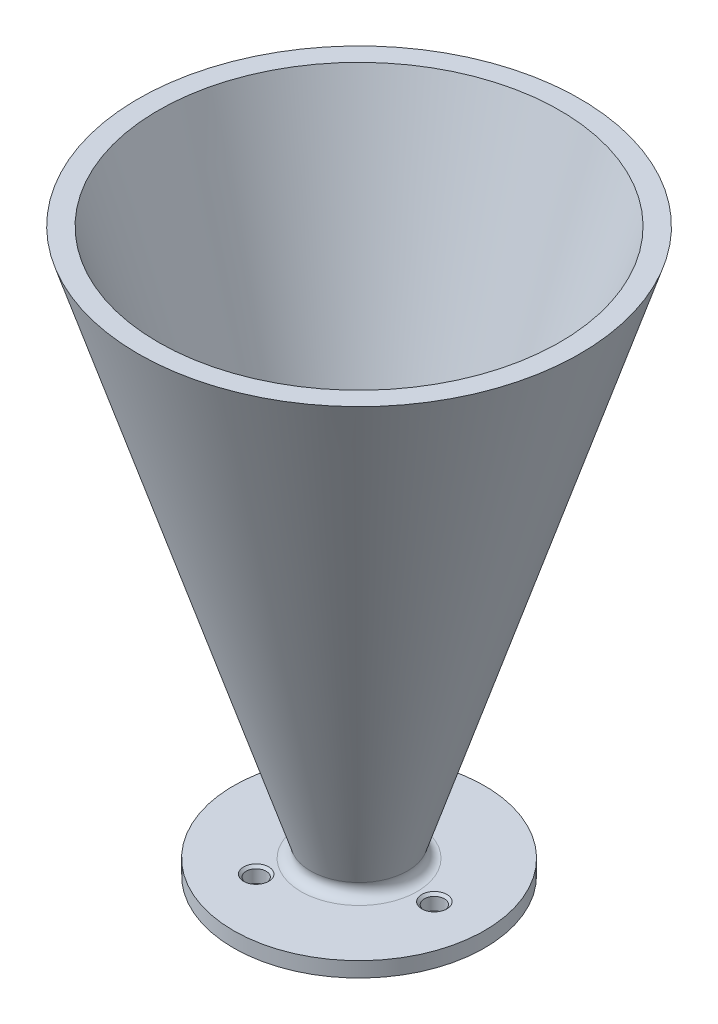
SolidWorks part; units mm, degrees
ref_plane "Front Plane" through (0, 0, 0) normal (0, 0, 1) x (1, 0, 0)
ref_plane "Top Plane" through (0, 0, 0) normal (0, 1, 0) x (1, 0, 0)
ref_plane "Right Plane" through (0, 0, 0) normal (1, 0, 0) x (0, 0, -1)
sketch "Sketch1" plane through (0, 0, 0) normal (0, 1, 0) x (1, 0, 0)
  circle A0 centre (0, 0) radius 4.8
  circle A1 centre (0, 0) radius 15 construction
  circle A2 centre (0, 0) radius 25
  dimension "D1" = 9.6
  dimension "D2" = 30
  dimension "D3" = 50
extrude "Boss-Extrude1" add sketch "Sketch1" along normal blind 3
sketch "Sketch5" plane through (0, 3, 0) normal (0, 1, 0) x (1, 0, 0)
  line L0 (0, 0) -> (15, 0) construction
  circle A0 centre (0, 0) radius 15
  circle A1 centre (15, 0) radius 2
  circle A2 centre (-7.5, -12.9904) radius 2
  circle A3 centre (-7.5, 12.9904) radius 2
  point P3 (15, 0)
  point P8 (-7.5, -12.9904)
  point P10 (-7.5, 12.9904)
  dimension "D1" = 30
  dimension "D2" = 4
  dimension "D4" = 15
  dimension "D3" = 3
hole_wizard "Ø4.0 (4) Diameter Hole1" positions "Sketch5" profile "Sketch7" hole size "Ø4.0" standard "ANSI Metric" end condition up to next
sketch "Sketch7" plane through (-7.5, 3, -12.9904) normal (1, 0, 0) x (0, 0, 1)
  line L0 (0, 0) -> (0, 3)
  line L1 (0, 3) -> (2, 3)
  line L2 (2, 3) -> (2, 0.5)
  line L3 (2, 0.5) -> (2.5, 0)
  line L5 (2.5, 0) -> (0, 0)
  line L6 (-2, 0.5) -> (-2.5, 0) construction
  line L11 (0, -6.35) -> (0, 107.95) construction
  dimension "Thru Hole Dia." = 4
  dimension "Thru Hole Depth" = 3
  dimension "Near C'Sink Dia." = 5
  dimension "Near C'Sink Angle" = 90
sketch "Sketch8" plane through (0, 0, 0) normal (0, 0, 1) x (1, 0, 0)
  line L0 (0, 0) -> (0, 110)
  line L1 (-4.8, 0) -> (0, 0) construction
  line L2 (40, 112) -> (44, 112)
  line L3 (0, 112) -> (40, 112) construction
  line L4 (4.8, 3) -> (8.8, 3)
  line L5 (0, 110) -> (0, 112)
  line L9 (0, 3) -> (4.8, 3)
  line L10 (25, 3) -> (-25, 3) construction
  line L11 (4.8, 3) -> (-4.8, 3) construction
  line L12 (40, 112) -> (4.8, 3)
  line L13 (8.8, 3) -> (44, 112)
  point P6 (0, 110)
  point P11 (0, 110)
  dimension "D1" = 110
  dimension "D2" = 4
  dimension "D3" = 2
  dimension "D4" = 40
  dimension "D5" = 4
  dimension "D6" = 4.8
revolve "Revolve1" add sketch "Sketch8" angle 360 about L0 region at (24.4, 57.5, 0)
fillet "Fillet1" radius 2 1 edges at (0, 3, 8.8)
